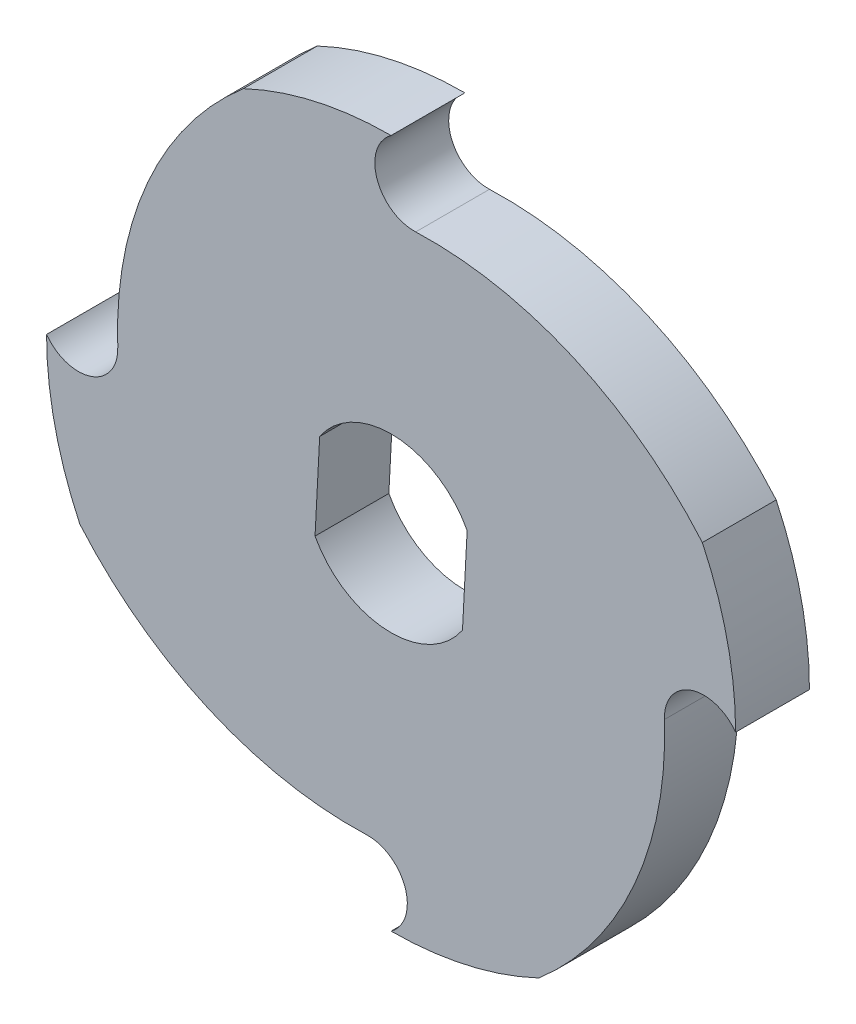
SolidWorks part; units mm, degrees
ref_plane "Front Plane" through (0, 0, 0) normal (0, 0, 1) x (1, 0, 0)
ref_plane "Top Plane" through (0, 0, 0) normal (0, 1, 0) x (1, 0, 0)
ref_plane "Right Plane" through (0, 0, 0) normal (1, 0, 0) x (0, 0, -1)
sketch "Çizim1" plane through (0, 0, 0) normal (0, 0, 1) x (1, 0, 0)
  arc A0 (-70, 0) -> (-63.2456, -30) centre (0, 0) ccw
  arc A1 (0, 70) -> (5, 55.5315) centre (4.6995, 63.5258) ccw
  arc A2 (5, 55.5315) -> (63.2456, 30) centre (7.7421, -17.417) cw
  arc A3 (70, 0) -> (55.5315, -5) centre (63.5258, -4.6995) ccw
  arc A4 (55.5315, -5) -> (30, -63.2456) centre (-17.417, -7.7421) cw
  arc A5 (0, -70) -> (-5, -55.5315) centre (-4.6995, -63.5258) ccw
  arc A6 (-5, -55.5315) -> (-63.2456, -30) centre (-7.7421, 17.417) cw
  arc A7 (-70, 0) -> (-55.5315, 5) centre (-63.5258, 4.6995) ccw
  arc A8 (-55.5315, 5) -> (-30, 63.2456) centre (17.417, 7.7421) cw
  arc A9 (0, 70) -> (-30, 63.2456) centre (0, 0) ccw
  arc A10 (70, 0) -> (63.2456, 30) centre (0, 0) ccw
  arc A11 (0, -70) -> (30, -63.2456) centre (0, 0) ccw
  point P26 (0, 0)
  dimension "D1" = 140
  dimension "D2" = 8
  dimension "D4" = 73
  dimension "D5" = 30
  dimension "D3" = 5
  dimension "D6" = 4
base flange "Taban-Flanş1" sketch "Çizim1" thickness 15 reverse thickness direction no parameters "D1"=0.7366
sketch "Çizim8" plane through (0, 0, 0) normal (0, 0, 1) x (1, 0, 0)
  line L0 (-15.4512, -8.2165) -> (-14.5077, 9.7866)
  line L1 (0, 0) -> (0, 5.5147) construction
  line L2 (0, 0) -> (0.22, 4.1977) construction
  line L3 (14.5077, -9.7866) -> (15.4512, 8.2165)
  arc A0 (-15.4512, -8.2165) -> (14.5077, -9.7866) centre (0, 0) ccw
  arc A1 (15.4512, 8.2165) -> (-14.5077, 9.7866) centre (0, 0) ccw
  dimension "D1" = 35
  dimension "D2" = 3
  dimension "D3" = 30
extrude "Kes-Ekstrüzyon1" cut sketch "Çizim8" against normal through all normal cut yes
sketch "Büküm-Çizgileri1" [suppressed] plane through (0, 0, 0) normal (0, 1, 0) x (1, 0, 0)
sketch "Sınırlandırma-Kutusu1" [suppressed] plane through (0, 0, 0) normal (0, 1, 0) x (1, 0, 0)
sheet metal parameters "Sac-Levha1" thickness 15 parameters "D1"=0.7366
flat pattern "Düz-Çoğaltma1" [suppressed]
sketch "Büküm-Çizgileri2" plane through (0, 0, 0) normal (0, 1, 0) x (1, 0, 0)
sketch3d "Sınırlandırma-Kutusu2" [suppressed]
  line L0 (-15.7402, -87.2309, 0) -> (-74.652, 20.5788, 0) construction
  line L1 (92.0683, -28.3197, 0) -> (33.1565, 79.4899, 0) construction
  line L2 (-15.7402, -87.2309, 0) -> (92.0683, -28.3197, 0) construction
  line L3 (-74.652, 20.5788, 0) -> (33.1565, 79.4899, 0) construction
sheet metal parameters "Sac-Levha2" thickness 15 parameters "D1"=0.7366
flat pattern "Düz-Çoğaltma1"
sketch "Büküm-Çizgileri2" plane through (0, 0, 0) normal (0, 1, 0) x (1, 0, 0)
sketch3d "Sınırlandırma-Kutusu2" [suppressed]
  line L0 (15.7402, -87.2309, 0) -> (74.652, 20.5788, 0) construction
  line L1 (-92.0683, -28.3197, 0) -> (-33.1565, 79.4899, 0) construction
  line L2 (15.7402, -87.2309, 0) -> (-92.0683, -28.3197, 0) construction
  line L3 (74.652, 20.5788, 0) -> (-33.1565, 79.4899, 0) construction
